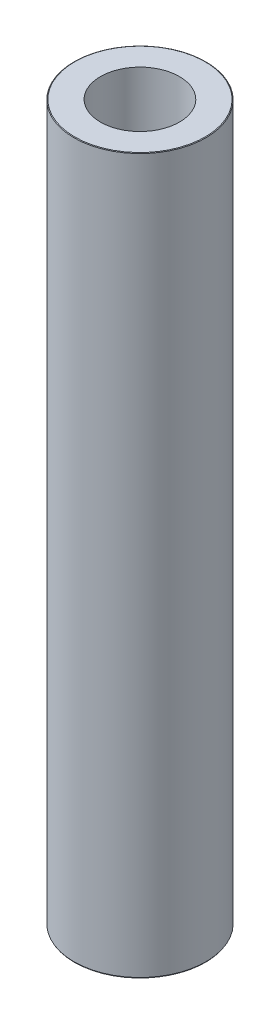
SolidWorks part; units mm, degrees
ref_plane "Front Plane" through (0, 0, 0) normal (0, 0, 1) x (1, 0, 0)
ref_plane "Top Plane" through (0, 0, 0) normal (0, 1, 0) x (1, 0, 0)
ref_plane "Right Plane" through (0, 0, 0) normal (1, 0, 0) x (0, 0, -1)
sketch "Sketch1" plane through (0, 0, 0) normal (0, 1, 0) x (1, 0, 0)
  circle A0 centre (0, 0) radius 40
  dimension "SHAFT_OD" = 80
extrude "Boss-Extrude1" add sketch "Sketch1" along normal blind 433.7196
sketch "Sketch2" plane through (0, 0, 0) normal (0, 1, 0) x (1, 0, 0)
  circle A0 centre (0, 0) radius 23.9783
  dimension "BORE_D" = 47.9566
extrude "Cut-Extrude1" cut sketch "Sketch2" along normal through all
chamfer "Chamfer1" distance 0.2561 angle 60 2 edges at (0, 433.7196, 40) (0, 0, 40) first distance on face at (0, 433.7196, 40) first distance on face at (0, 0, 23.9783)
